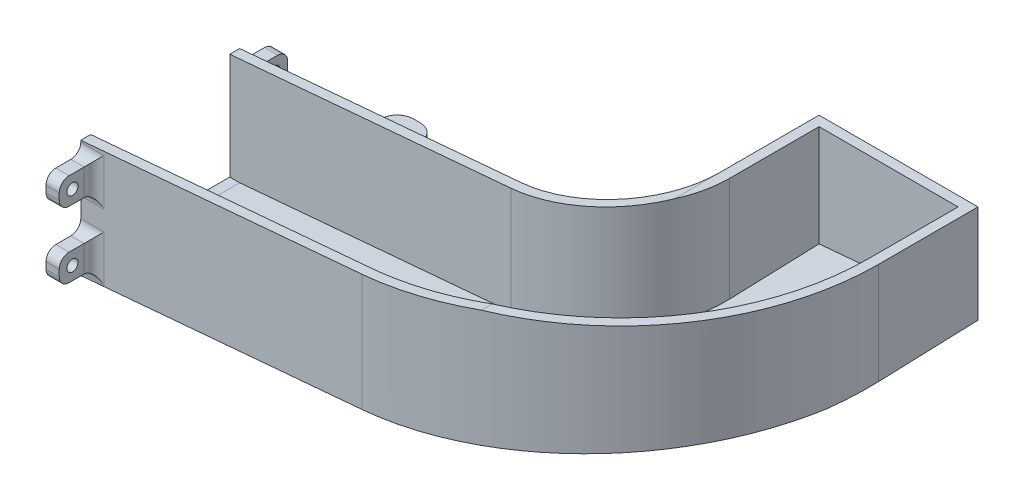
SolidWorks part; units mm, degrees
ref_plane "Front Plane" through (0, 0, 0) normal (0, 0, 1) x (1, 0, 0)
ref_plane "Top Plane" through (0, 0, 0) normal (0, 1, 0) x (1, 0, 0)
ref_plane "Right Plane" through (0, 0, 0) normal (1, 0, 0) x (0, 0, -1)
sketch "Sketch2" plane through (0, 0, 0) normal (0, 1, 0) x (1, 0, 0)
  line L1 (0, 0) -> (85, 0)
  line L2 (0, 0) -> (0, 48)
  line L3 (0, 48) -> (85, 48)
  line L8 (115, 78) -> (115, 108)
  line L9 (115, 108) -> (163, 108)
  line L10 (163, 78) -> (163, 108)
  arc A1 (85, 48) -> (115, 78) centre (85, 78) ccw
  arc A2 (85, 0) -> (163, 78) centre (85, 78) ccw
  point P9 (0, 0)
  point P11 (0, 0)
  dimension "D1" = 48
  dimension "D5" = 30
  dimension "D2" = 85
  dimension "D3" = 48
  dimension "D4" = 115
extrude "Boss-Extrude1" add sketch "Sketch2" along normal blind 50
sketch "Sketch3" plane through (0, 0, 0) normal (0, 0, 1) x (1, 0, 0)
  line L0 (0, 0) -> (200, 17.4977)
  line L2 (0, 50) -> (0, 0) construction
  line L3 (200, 0) -> (200, 17.4977)
  line L5 (0, 0) -> (200, 0)
  line L7 (0, 35.39) -> (0, 50)
  line L8 (0, 50) -> (200, 50)
  line L9 (0, 50) -> (85, 50) construction
  line L11 (163, 50) -> (85, 50) construction
  line L12 (0, 35.39) -> (115, 45.4512)
  line L13 (115, 45.4512) -> (200, 45.4512)
  line L14 (200, 45.4512) -> (200, 50)
  point P4 (140.9944, 57.1439)
  point P14 (154.6463, 60)
  point P17 (180.8999, 60)
  point P18 (132.5245, 57.8644)
  point P21 (113.8292, 56.2288)
  point P23 (0, 0)
  dimension "D1" = 35.39
  dimension "D2" = 200
  dimension "D3" = 5
extrude "Cut-Extrude1" cut sketch "Sketch3" against normal through all
sketch "Sketch18" plane through (163, 0, 0) normal (-1, 0, 0) x (0, 0, 1)
  line L0 (-123, 8.2607) -> (-53, 8.2607)
  line L4 (-123, 8.2607) -> (-123, 16.3451)
  line L5 (-48, 35.39) -> (-48, 0) construction
  line L6 (-78, 14.2607) -> (-108, 14.2607) construction
  line L7 (-53, 8.2607) -> (-53, 13.9006)
  line L8 (-53, 13.9006) -> (-123, 16.3451)
  ellipse E3 centre (-78, 7.4365) end of major axis (0, 7.4365) minor radius 6.8241 (0, 7.4365) -> (-78, 14.2607) ccw construction
  dimension "D1" = 2
  dimension "D2" = 70
  dimension "D3" = 6
  dimension "D4" = 5
extrude "Cut-Extrude9" cut sketch "Sketch18" along direction (-0.9962, -0.0872, 0) on the side against the normal blind 55 and the other way blind 55
shell "Shell4" thickness 3 removed face at (67.7517, 41.3175, -28.7169) removed face at (136.38, 45.4512, -74.1467)
sketch "Sketch15" plane through (3, 0, 0) normal (1, 0, 0) x (0, 0, -1)
  line L4 (45, 35.6525) -> (3, 35.6525)
  line L5 (45, 35.6525) -> (3, 35.6525)
  line L8 (3, 35.6525) -> (3, 3.2739)
  line L9 (3, 3.2739) -> (45, 3.2739)
  line L10 (45, 3.2739) -> (45, 35.6525)
  line L12 (3, 35.6525) -> (3, 3.2739)
  line L13 (3, 3.2739) -> (45, 3.2739)
  line L14 (45, 3.2739) -> (45, 35.6525)
  dimension "D1" = 0
extrude "Cut-Extrude8" cut sketch "Sketch15" against normal up to surface (3 mm away) up to face at (0, 17.695, -24)
sketch "Sketch16" plane through (0, 0, 0) normal (-1, 0, 0) x (0, 0, 1)
  line L1 (-1.5, 31.89) -> (10.5, 31.89)
  line L2 (-1.5, 31.89) -> (-1.5, 23.89)
  line L3 (-1.5, 23.89) -> (10.5, 23.89)
  line L4 (10.5, 31.89) -> (10.5, 23.89)
  line L5 (0, 35.39) -> (0, 0) construction
  line L7 (-3, 35.39) -> (0, 35.39) construction
  line L8 (-1.5, 11.89) -> (10.5, 11.89)
  line L13 (-1.5, 11.89) -> (-1.5, 3.89)
  line L14 (-1.5, 3.89) -> (10.5, 3.89)
  line L15 (10.5, 11.89) -> (10.5, 3.89)
  line L16 (-24, 0) -> (-24, 60) construction
  line L17 (-48, 0) -> (0, 0) construction
  line L18 (-58.5, 11.89) -> (-58.5, 3.89)
  line L19 (-46.5, 3.89) -> (-58.5, 3.89)
  line L20 (-46.5, 11.89) -> (-46.5, 3.89)
  line L21 (-46.5, 11.89) -> (-58.5, 11.89)
  line L22 (-58.5, 31.89) -> (-58.5, 23.89)
  line L23 (-46.5, 23.89) -> (-58.5, 23.89)
  line L24 (-46.5, 31.89) -> (-46.5, 23.89)
  line L25 (-46.5, 31.89) -> (-58.5, 31.89)
  circle A0 centre (6.5, 27.89) radius 1.7
  circle A2 centre (6.5, 7.89) radius 1.7
  circle A3 centre (-54.5, 7.89) radius 1.7
  circle A4 centre (-54.5, 27.89) radius 1.7
  point P10 (10.5, 27.89)
  dimension "D1" = 3.4
  dimension "D2" = 8
  dimension "D3" = 4
  dimension "D4" = 1.5
  dimension "D5" = 3.5
  dimension "D6" = 8
  dimension "D7" = 2
  dimension "D8" = 20
  dimension "D9" = 60
extrude "Boss-Extrude2" add sketch "Sketch16" against normal blind 4
fillet "Fillet1" radius 3 20 edges at (2, 3.89, 10.5) (2, 3.89, 0) (4, 7.89, 0) (2, 11.89, 10.5) (2, 11.89, 0) (2, 23.89, 10.5) (2, 23.89, 0) (4, 27.89, 0) (2, 31.89, 0) (2, 31.89, 10.5) (2, 11.89, -58.5) (2, 3.89, -58.5) (2, 3.89, -48) (4, 7.89, -48) (2, 11.89, -48) (4, 27.89, -48) (2, 23.89, -48) (2, 23.89, -58.5) (2, 31.89, -48) (2, 31.89, -58.5)
sketch "Sketch19" plane through (0, 45.4512, 0) normal (0, 1, 0) x (1, 0, 0)
  line L0 (115, 108) -> (163, 108) construction
  line L2 (115, 108) -> (115, 78) construction
  line L3 (115, 90.77) -> (91.77, 90.77)
  line L4 (115, 90.77) -> (115, 78.77)
  line L5 (115, 78.77) -> (91.77, 78.77)
  line L6 (91.77, 90.77) -> (91.77, 78.77)
  line L7 (0, 48) -> (85, 48) construction
  line L8 (75.77, 48) -> (87.77, 48)
  line L9 (75.77, 48) -> (75.77, 72.77)
  line L10 (75.77, 72.77) -> (87.77, 72.77)
  line L11 (87.77, 48) -> (87.77, 72.77)
  line L29 (22.77, 48) -> (34.77, 48)
  line L34 (22.77, 48) -> (22.77, 72.77)
  line L35 (22.77, 72.77) -> (34.77, 72.77)
  line L36 (34.77, 48) -> (34.77, 72.77)
  circle A0 centre (97.77, 84.77) radius 2.2
  circle A1 centre (81.77, 66.77) radius 2.2
  circle A4 centre (28.77, 66.77) radius 2.2
  point P11 (91.77, 84.77)
  point P20 (81.77, 72.77)
  line M10 (115, 108) -> (115, 78)
  dimension "D3" = 4.4
  dimension "D8" = 12
  dimension "D11" = 53
  dimension "D1" = 23.23
  dimension "D2" = 17.23
  dimension "D4" = 12
  dimension "D5" = 6
  dimension "D6" = 41.23
  dimension "D7" = 33.23
  dimension "D9" = 6
  dimension "D10" = 2
extrude "Boss-Extrude3" add sketch "Sketch19" against normal blind 5 from offset 27 contours L34 | L34 | L8 L11 L10 L9 A1 | L3 L6 L5 A0 M10 region at (103.7089, 45.4512, -84.77) region at (81.77, 45.4512, -60.0408) region at (28.77, 45.4512, -60.0408) offset against normal yes
fillet "Fillet6" radius 5 19 edges at (86.3865, 18.4512, -48.0321) (86.3865, 13.4512, -48.0321) (115, 13.4512, -84.77) (115, 15.9512, -90.77) (115, 18.4512, -84.77) (87.77, 15.9512, -48.1282) (80.385, 18.4512, -48) (75.77, 15.9512, -48) (80.385, 13.4512, -48) (28.77, 13.4512, -48) (34.77, 15.9512, -48) (22.77, 15.9512, -48) (28.77, 18.4512, -48) (22.77, 15.9512, -72.77) (34.77, 15.9512, -72.77) (87.77, 15.9512, -72.77) (75.77, 15.9512, -72.77) (91.77, 15.9512, -90.77) (91.77, 15.9512, -78.77)
fillet "Fillet9" radius 0.5 1 edges at (115, 17.0261, -78.77)
